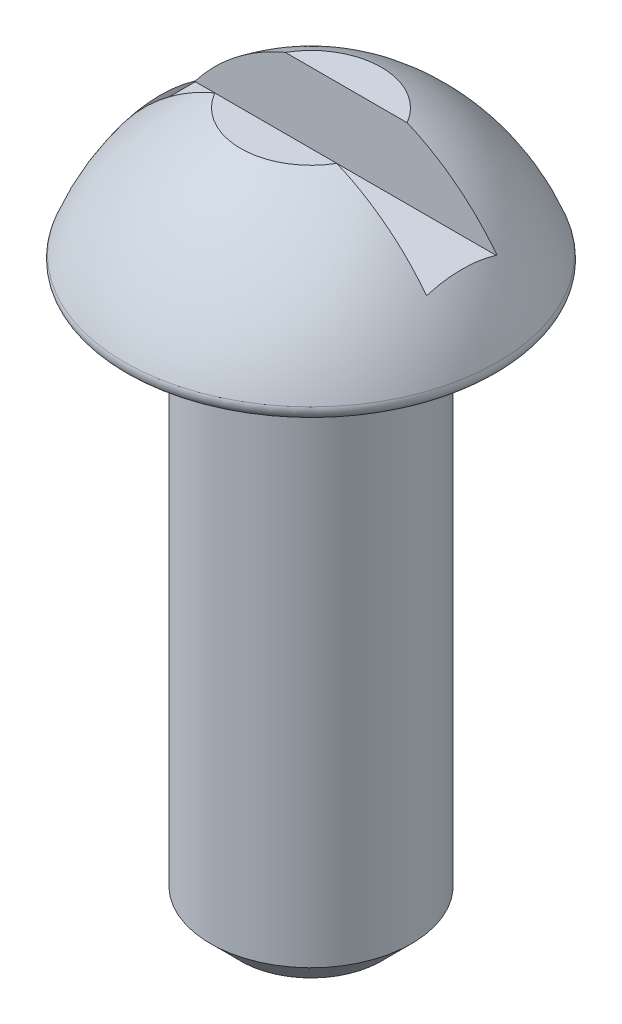
SolidWorks part; units mm, degrees
ref_plane "Спереди" through (0, 0, 0) normal (0, 0, 1) x (1, 0, 0)
ref_plane "Сверху" through (0, 0, 0) normal (0, 1, 0) x (1, 0, 0)
ref_plane "Справа" through (0, 0, 0) normal (1, 0, 0) x (0, 0, -1)
sketch "Эскиз1" plane through (0, 0, 0) normal (0, 0, 1) x (1, 0, 0)
  line L0 (1.9, 5.6) -> (1, 5.6)
  line L1 (0, 0) -> (0, 7)
  line L2 (1, 5.6) -> (1, 0.3)
  line L3 (1, 0.3) -> (0.7, 0)
  line L4 (0.7, 0) -> (0, 0)
  line L5 (0, 7) -> (0.7, 7)
  arc A0 (0.7, 7) -> (1.9, 5.6) centre (-0.307, 4.9226) cw
  dimension "D2" = 0.7
  dimension "D8" = 2.1
  dimension "D1" = 7
  dimension "D3" = 1
  dimension "D4" = 0.7
  dimension "D5" = 1.4
  dimension "D6" = 1.9
  dimension "D7" = 45
revolve "Повернуть1" add sketch "Эскиз1" angle 360 about L1
fillet "Скругление1" radius 0.1 1 edges at (0, 5.6, -1.9)
ref_axis "Ось1" through (0, -104.1565, 0) along (0, 1, 0)
sketch "Эскиз2" plane through (0, 7, 0) normal (0, 1, 0) x (-1, 0, 0)
  line L1 (1.5, -0.35) -> (-1.5, -0.35)
  line L2 (1.5, -0.35) -> (1.5, 0.35)
  line L3 (1.5, 0.35) -> (-1.5, 0.35)
  line L4 (-1.5, -0.35) -> (-1.5, 0.35)
  dimension "D1" = 0.7
  dimension "D2" = 0.35
  dimension "D3" = 3
  dimension "D4" = 1.5
extrude "Вырез-Вытянуть1" cut sketch "Эскиз2" against normal blind 0.7
